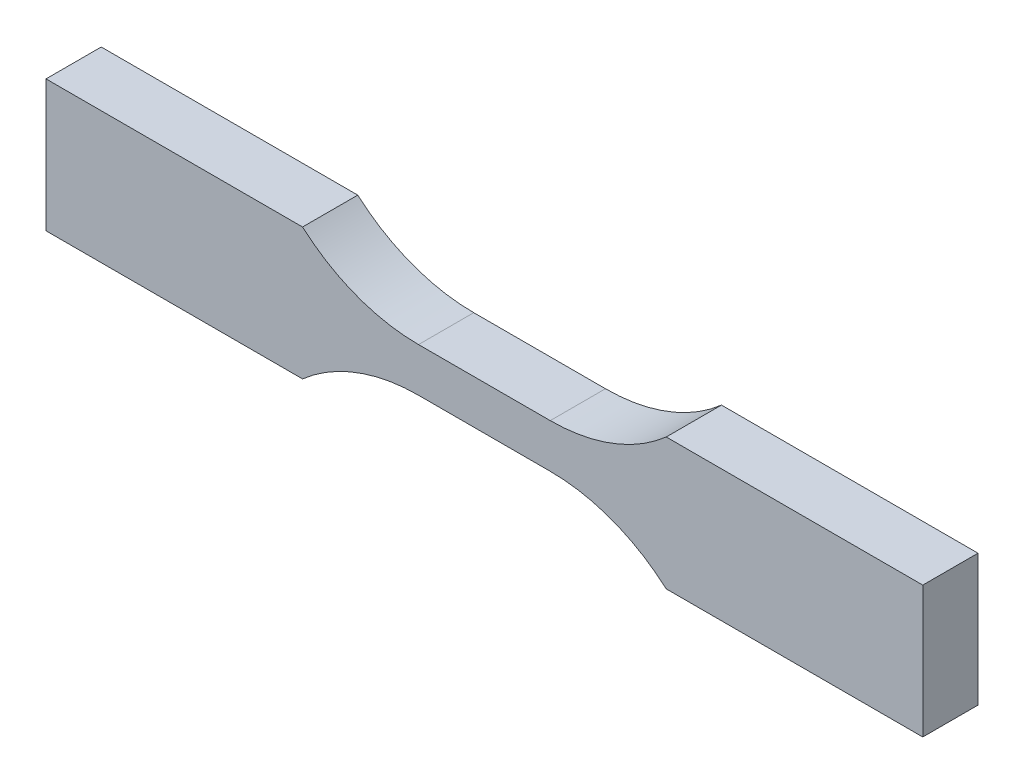
SolidWorks part; units mm, degrees
ref_plane "Front Plane" through (0, 0, 0) normal (0, 0, 1) x (1, 0, 0)
ref_plane "Top Plane" through (0, 0, 0) normal (0, 1, 0) x (1, 0, 0)
ref_plane "Right Plane" through (0, 0, 0) normal (1, 0, 0) x (0, 0, -1)
sketch "Sketch1" plane through (0, 0, 0) normal (0, 0, 1) x (1, 0, 0)
  line L0 (0, 0) -> (0, 9.53)
  line L1 (0, 9.53) -> (18.58, 9.53)
  line L2 (18.58, 9.53) -> (18.58, 6.355)
  line L3 (18.58, 6.355) -> (44.92, 6.355)
  line L4 (44.92, 6.355) -> (44.92, 9.53)
  line L5 (44.92, 9.53) -> (63.5, 9.53)
  line L6 (63.5, 9.53) -> (63.5, 0)
  line L7 (63.5, 0) -> (44.92, 0)
  line L8 (44.92, 0) -> (44.92, 3.175)
  line L9 (44.92, 3.175) -> (18.58, 3.175)
  line L10 (18.58, 3.175) -> (18.58, 0)
  line L11 (18.58, 0) -> (0, 0)
  dimension "D1" = 9.53
  dimension "D2" = 3.18
  dimension "D3" = 63.5
  dimension "D4" = 18.58
extrude "Boss-Extrude1" add sketch "Sketch1" along normal mid plane 4
fillet "Fillet1" radius 12.7 2 edges at (44.92, 3.175, 0) (18.58, 3.175, 0)
fillet "Fillet2" radius 12.7 2 edges at (44.92, 6.355, 0) (18.58, 6.355, 0)
